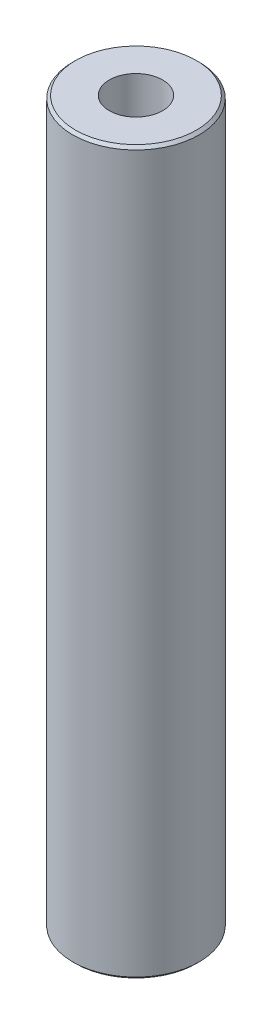
SolidWorks part; units mm, degrees
ref_plane "Front Plane" through (0, 0, 0) normal (0, 0, 1) x (1, 0, 0)
ref_plane "Top Plane" through (0, 0, 0) normal (0, 1, 0) x (1, 0, 0)
ref_plane "Right Plane" through (0, 0, 0) normal (1, 0, 0) x (0, 0, -1)
sketch "Sketch1" plane through (0, 0, 0) normal (0, 1, 0) x (1, 0, 0)
  circle A0 centre (0, 0) radius 52.5
  dimension "SHAFT_OD" = 105
extrude "Boss-Extrude1" add sketch "Sketch1" along normal blind 600
sketch "Sketch2" plane through (0, 0, 0) normal (0, 1, 0) x (1, 0, 0)
  circle A0 centre (0, 0) radius 22.1851
  dimension "BORE_D" = 44.3703
extrude "Cut-Extrude1" cut sketch "Sketch2" along normal through all
chamfer "Chamfer1" distance 2.2837 angle 45 2 edges at (0, 600, 52.5) (0, 0, 52.5)
